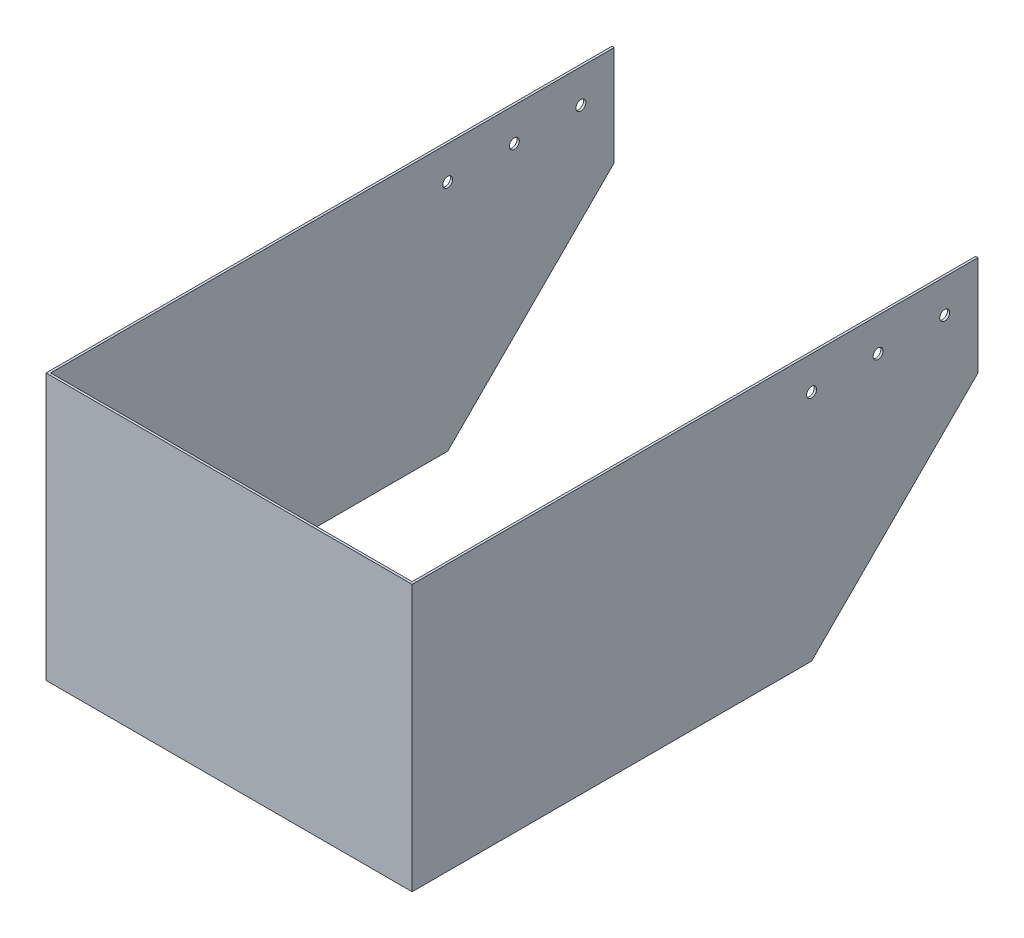
SolidWorks part; units mm, degrees
ref_plane "Front Plane" through (0, 0, 0) normal (0, 0, 1) x (1, 0, 0)
ref_plane "Top Plane" through (0, 0, 0) normal (0, 1, 0) x (1, 0, 0)
ref_plane "Right Plane" through (0, 0, 0) normal (1, 0, 0) x (0, 0, -1)
sketch "Sketch1" plane through (0, 0, 0) normal (0, 1, 0) x (1, 0, 0)
  line L1 (0, 0) -> (110, 0)
  line L2 (0, 0) -> (0, 170)
  line L3 (0, 170) -> (110, 170)
  line L4 (110, 0) -> (110, 170)
  dimension "D1" = 110
  dimension "D2" = 170
extrude "Boss-Extrude1" add sketch "Sketch1" along normal blind 80
sketch "Sketch2" plane through (0, 80, 0) normal (0, 1, 0) x (1, 0, 0)
  line L0 (110, 170) -> (0, 170) construction
  line L1 (0.7, 170) -> (109.3, 170)
  line L2 (0.7, 170) -> (0.7, 0.7)
  line L3 (0.7, 0.7) -> (109.3, 0.7)
  line L4 (109.3, 170) -> (109.3, 0.7)
  line L6 (0, 0) -> (110, 0) construction
  line L7 (0, 170) -> (0, 0) construction
  line L8 (110, 0) -> (110, 170) construction
  dimension "D1" = 0.7
  dimension "D2" = 0.7
  dimension "D3" = 0.7
extrude "Cut-Extrude1" cut sketch "Sketch2" against normal through all
sketch "Sketch4" plane through (110, 0, 0) normal (1, 0, 0) x (0, 0, -1)
  line L0 (0, 80) -> (170, 80) construction
  line L1 (170, 80) -> (170, 0) construction
  line L2 (160, 70) -> (129.2817, 70) construction
  circle A0 centre (160, 70) radius 1.5
  circle A1 centre (120, 70) radius 1.5
  circle A2 centre (140, 70) radius 1.5
  dimension "D2" = 3
  dimension "D4" = 20
  dimension "D1" = 10
  dimension "D3" = 10
  dimension "D5" = 20
extrude "Cut-Extrude3" cut sketch "Sketch4" against normal through all
sketch "Sketch8" plane through (110, 0, 0) normal (1, 0, 0) x (0, 0, -1)
  line L0 (170, 50) -> (120, 0)
  line L1 (170, 80) -> (170, 0) construction
  line L2 (0, 0) -> (170, 0) construction
  line L3 (170, 50) -> (170, 0)
  line L4 (170, 0) -> (120, 0)
  dimension "D1" = 50
  dimension "D2" = 50
extrude "Cut-Extrude5" cut sketch "Sketch8" against normal through all
